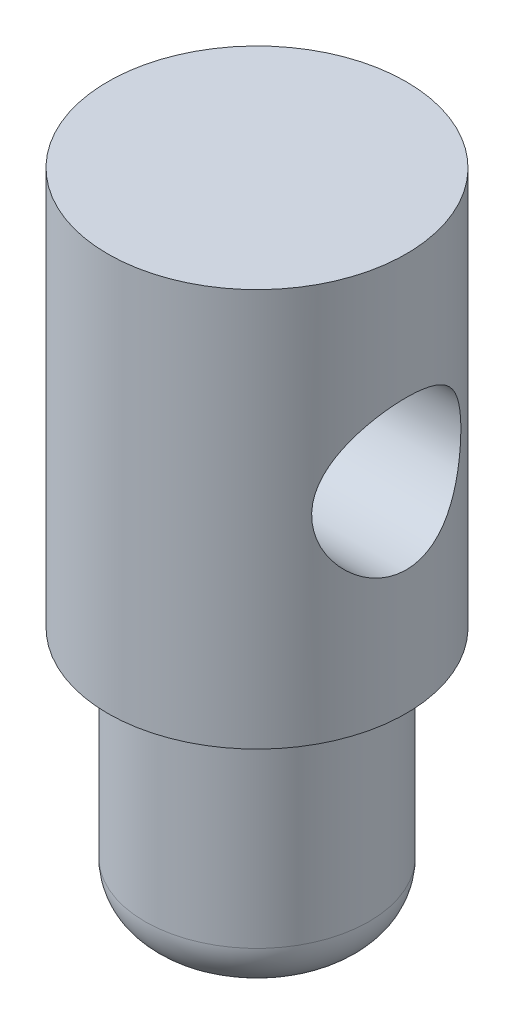
SolidWorks part; units mm, degrees
ref_plane "Front Plane" through (0, 0, 0) normal (0, 0, 1) x (1, 0, 0)
ref_plane "Top Plane" through (0, 0, 0) normal (0, 1, 0) x (1, 0, 0)
ref_plane "Right Plane" through (0, 0, 0) normal (1, 0, 0) x (0, 0, -1)
sketch "Sketch1" plane through (0, 0, 0) normal (0, 1, 0) x (1, 0, 0)
  line L0 (0, 3) -> (0, -3) construction
  line L1 (1.5, 2.5981) -> (1.5, -2.5981)
  line L2 (-1.5, 2.5981) -> (-1.5, -2.5981)
  circle A0 centre (0, 0) radius 3
  circle A1 centre (0, 0) radius 2.25
  dimension "D1" = 4.5
  dimension "D2" = 6
  dimension "D3" = 1.5
  dimension "D4" = 1.5
extrude "Boss-Extrude1" add sketch "Sketch1" along normal blind 2 contours A1 L2 A0 | L2 A1 | L0 A0 L2 A1 | L0 A1 L2 A0 | A0 L0 A1 L1 | A1 L0 A0 L1 | A1 L1 A0 | L1 A1 region at (0.7748, 0, -2.4613) region at (-0.7748, 0, -2.4613) region at (2.2579, 0, 0) region at (-2.2579, 0, 0) region at (0.7748, 0, 2.4613) region at (-0.7748, 0, 2.4613) region at (1.8047, 0, 0) region at (-1.8047, 0, 0)
extrude "Boss-Extrude2" add sketch "Sketch1<4>" along normal blind 8 contours A1 L0 L1 | L0 A1 L2 | A0 L0 A1 L1 | L0 A0 L2 A1 | A1 L0 A0 L1 | L0 A1 L2 A0 | A1 L2 A0 | L2 A1 | A1 L1 A0 | L1 A1 region at (0.7748, 0, -2.4613) region at (-0.7748, 0, -2.4613) region at (0.7165, 0, 0) region at (-0.7165, 0, 0) region at (2.2579, 0, 0) region at (-2.2579, 0, 0) region at (0.7748, 0, 2.4613) region at (-0.7748, 0, 2.4613) region at (1.8047, 0, 0) region at (-1.8047, 0, 0)
sketch "Sketch1<4>" plane through (0, 0, 0) normal (0, 1, 0) x (1, 0, 0) same geometry as "Sketch1"
extrude "Boss-Extrude3" add sketch "Sketch1<5>" against normal blind 5 contours L2 A1 | L0 A1 L2 | A1 L0 L1 | L1 A1 region at (0.7165, 0, 0) region at (-0.7165, 0, 0) region at (1.8047, 0, 0) region at (-1.8047, 0, 0)
sketch "Sketch1<5>" plane through (0, 0, 0) normal (0, 1, 0) x (1, 0, 0) same geometry as "Sketch1"
sketch "Sketch2" plane through (0, 0, 0) normal (1, 0, 0) x (0, 0, -1)
  circle A0 centre (0, 4) radius 1.5
  dimension "D2" = 3
  dimension "D1" = 4
extrude "Cut-Extrude1" cut sketch "Sketch2" against normal through all both and the other way through all
fillet "Fillet1" radius 1 1 edges at (0, -5, 2.25)
